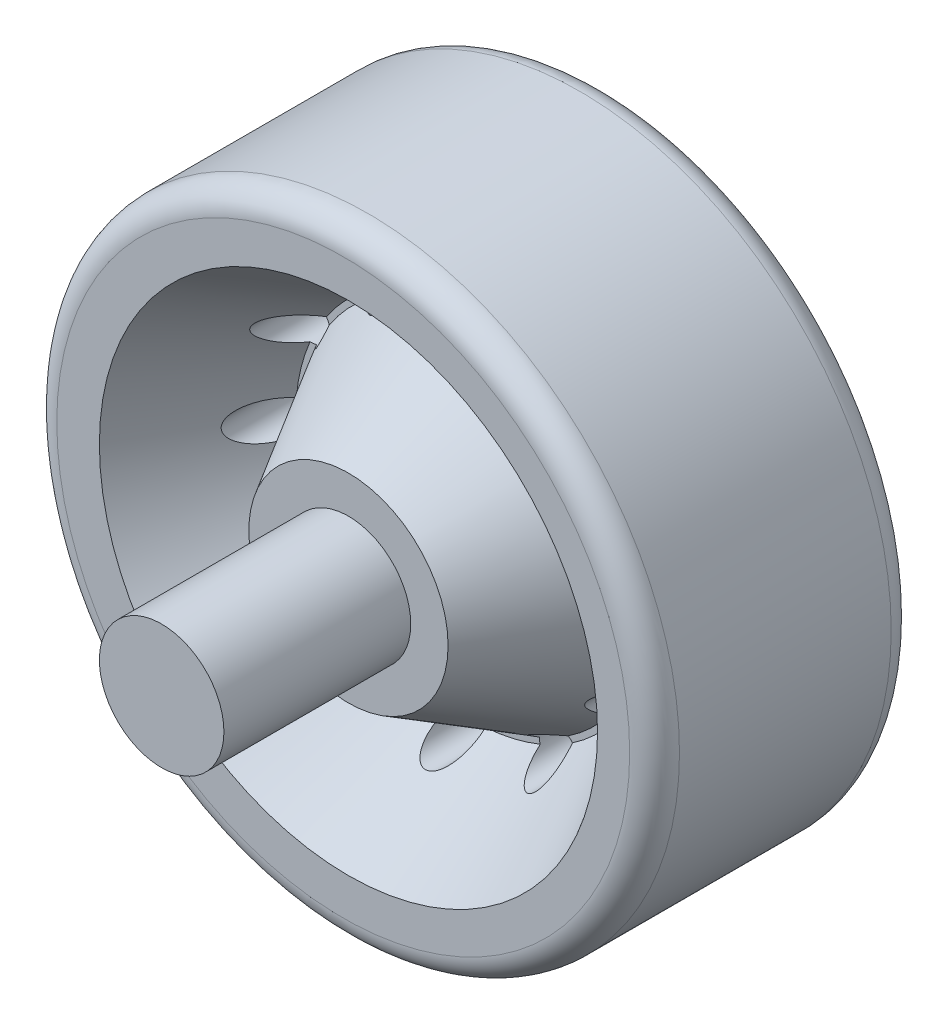
SolidWorks part; units mm, degrees
ref_plane "Front Plane" through (0, 0, 0) normal (0, 0, 1) x (1, 0, 0)
ref_plane "Top Plane" through (0, 0, 0) normal (0, 1, 0) x (1, 0, 0)
ref_plane "Right Plane" through (0, 0, 0) normal (1, 0, 0) x (0, 0, -1)
sketch "Sketch1" plane through (0, 0, 0) normal (0, 0, 1) x (1, 0, 0)
  circle A0 centre (0, 0) radius 25
  dimension "D1" = 50
extrude "Boss-Extrude1" add sketch "Sketch1" along normal blind 21
sketch "Sketch2" plane through (2.2781, 2.6607, 21) normal (0, 0, 1) x (1, 0, 0)
  circle A0 centre (-1.8579, -2.4947) radius 5
  dimension "D1" = 10
extrude "Boss-Extrude2" add sketch "Sketch2" along normal blind 15
fillet "Fillet3" radius 2 2 edges at (25, 0, 21) (25, 0, 0)
sketch "Sketch3" plane through (0, 0, 0) normal (0, 0, -1) x (-1, 0, 0)
  circle A0 centre (0, 0) radius 17.5
  circle A1 centre (0, 0) radius 5
  dimension "D1" = 35
  dimension "D2" = 10
extrude "Cut-Extrude3" cut sketch "Sketch3" against normal blind 10 draft 30
sketch "Sketch4" plane through (0, 0, 0) normal (0, 0, -1) x (-1, 0, 0)
  circle A0 centre (0, 0) radius 7.5
  dimension "D1" = 15
extrude "Cut-Extrude6" cut sketch "Sketch4" against normal blind 3
sketch "Sketch6" plane through (0, 0, 3) normal (0, 0, -1) x (-1, 0, 0)
  circle A0 centre (0, 0) radius 5
  dimension "D1" = 10
extrude "Boss-Extrude7" add sketch "Sketch6" along normal blind 5
sketch "Sketch8" plane through (0, 0, 0) normal (0, 0, -1) x (-1, 0, 0)
  circle A0 centre (0, 0) radius 20
  circle A1 centre (0, 0) radius 23 construction
  circle A2 centre (0, 0) radius 23
  dimension "D1" = 40
extrude "Boss-Extrude8" add sketch "Sketch8" along normal blind 0.25
sketch "Sketch9" plane through (0, 0, -2) normal (0, 0, -1) x (-1, 0, 0)
  circle A0 centre (3.5, 0) radius 0.75
  circle A1 centre (2.505, -2.4021) radius 0.75
  circle A2 centre (0.1029, -3.3971) radius 0.75
  circle A3 centre (-2.2992, -2.4021) radius 0.75
  circle A4 centre (-3.2941, 0) radius 0.75
  circle A5 centre (-2.2992, 2.4021) radius 0.75
  circle A6 centre (0.1029, 3.3971) radius 0.75
  circle A7 centre (2.505, 2.4021) radius 0.75
  dimension "D1" = 1.5
  dimension "D3" = 8
extrude "Cut-Extrude9" cut sketch "Sketch9" against normal blind 22
sketch "Sketch12" plane through (0, 0, -2) normal (0, 0, -1) x (-1, 0, 0)
  circle A0 centre (14.5, 0) radius 1.5
  circle A1 centre (12.5574, -7.25) radius 1.5
  circle A2 centre (7.25, -12.5574) radius 1.5
  circle A3 centre (0, -14.5) radius 1.5
  circle A4 centre (-7.25, -12.5574) radius 1.5
  circle A5 centre (-12.5574, -7.25) radius 1.5
  circle A6 centre (-14.5, 0) radius 1.5
  circle A7 centre (-12.5574, 7.25) radius 1.5
  circle A8 centre (-7.25, 12.5574) radius 1.5
  circle A9 centre (0, 14.5) radius 1.5
  circle A10 centre (7.25, 12.5574) radius 1.5
  circle A11 centre (12.5574, 7.25) radius 1.5
  circle A12 centre (-2.2992, -2.4021) radius 0.75 construction
  dimension "D1" = 3
  dimension "D2" = 14.5
  dimension "D4" = 9.5492
  dimension "D3" = 12
extrude "Cut-Extrude11" cut sketch "Sketch12" against normal blind 25 contours A10 | A9 | A8 | A0 | A1 | A2 | A3 | A4 | A5 | A6 | A7 | A11 region at (-14.5, 0, -2) region at (-12.5574, -7.25, -2) region at (-7.25, -12.5574, -2) region at (0, -14.5, -2) region at (7.25, -12.5574, -2) region at (12.5574, -7.25, -2) region at (14.5, 0, -2) region at (12.5574, 7.25, -2) region at (7.25, 12.5574, -2) region at (0, 14.5, -2) region at (-7.25, 12.5574, -2)
fillet "Fillet6" radius 1.5 2 edges at (-5, 0, 3) (-5, 0, -2)
sketch "Sketch13" plane through (0, 0, 21) normal (0, 0, 1) x (1, 0, 0)
  circle A0 centre (0.4202, 0.1659) radius 8
  circle A1 centre (0.4202, 0.1659) radius 20
  dimension "D1" = 16
  dimension "D2" = 40
extrude "Cut-Extrude12" cut sketch "Sketch13" against normal blind 10 draft 30
scale "Scale1" bodies to scale 125 scale about centroid uniform scaling yes scale factor 0.5
